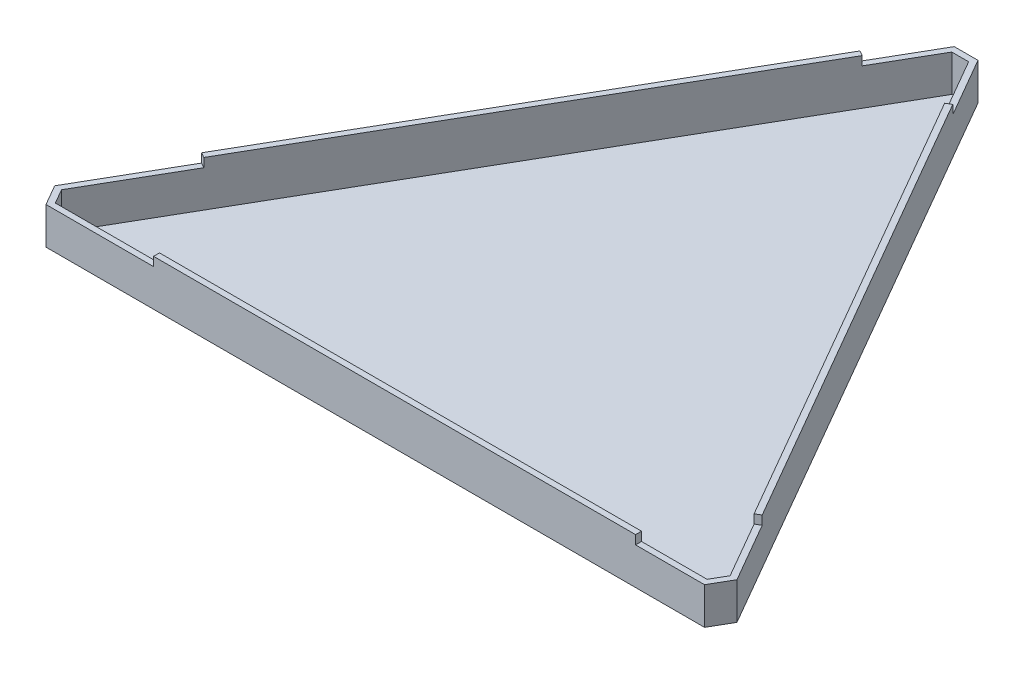
SolidWorks part; units mm, degrees
note: The reader was unsure of these and kept them because the rebuilt part matched: shared geometry of "Sketch1<3>", "Sketch1<4>".
ref_plane "Front Plane" through (0, 0, 0) normal (0, 0, 1) x (1, 0, 0)
ref_plane "Top Plane" through (0, 0, 0) normal (0, 1, 0) x (1, 0, 0)
ref_plane "Right Plane" through (0, 0, 0) normal (1, 0, 0) x (0, 0, -1)
sketch "Sketch1" plane through (0, 0, 0) normal (0, 1, 0) x (1, 0, 0)
  line L7 (-115, 0) -> (-111, -6.9282)
  line L9 (115, 0) -> (111, -6.9282)
  line L17 (-4, 192.2576) -> (111, -6.9282) construction
  line L20 (4, 192.2576) -> (-4, 192.2576)
  line L24 (4, 192.2576) -> (-111, -6.9282) construction
  line L25 (-115, 0) -> (115, 0) construction
  line L26 (-112.6906, 0) -> (-95.1379, 30.4021)
  line L27 (-113, -3.4641) -> (-107, 0) construction
  line L28 (0, 192.2576) -> (0, 185.3294) construction
  line L29 (113, -3.4641) -> (107, 0) construction
  line L30 (59.5, 96.1288) -> (57.7679, 95.1288) construction
  line L31 (-59.5, 96.1288) -> (-57.7679, 95.1288) construction
  line L33 (-112.6906, 0) -> (-109.8453, -4.9282)
  line L36 (112.6906, 0) -> (109.8453, -4.9282)
  line L37 (-2.8453, 190.2576) -> (2.8453, 190.2576)
  line L43 (87.75, -6.9282) -> (111, -6.9282)
  line L45 (87.75, -4.9282) -> (87.75, -6.9282)
  line L46 (-74.74, -4.9282) -> (87.75, -4.9282)
  line L49 (87.75, -6.9282) -> (-74.74, -6.9282)
  line L50 (-96.87, 31.4021) -> (-115, 0)
  line L51 (-15.625, 172.1225) -> (-96.87, 31.4021)
  line L52 (-15.625, 172.1225) -> (-13.8929, 171.1225)
  line L53 (-95.1379, 30.4021) -> (-13.8929, 171.1225)
  line L54 (-15.625, 172.1225) -> (-4, 192.2576)
  line L55 (-109.8453, -4.9282) -> (-74.74, -4.9282)
  line L56 (109.8453, -4.9282) -> (87.75, -4.9282)
  line L57 (-111, -6.9282) -> (-74.74, -6.9282)
  line L59 (-2.8453, 190.2576) -> (-13.8929, 171.1225)
  line L60 (115, 0) -> (103.375, 20.1351)
  line L61 (15.625, 172.1225) -> (13.8929, 171.1225)
  line L62 (103.375, 20.1351) -> (101.6429, 19.1351)
  line L63 (101.6429, 19.1351) -> (112.6906, 0)
  line L64 (2.8453, 190.2576) -> (13.8929, 171.1225)
  line L65 (4, 192.2576) -> (15.625, 172.1225)
  line L66 (15.625, 172.1225) -> (103.375, 20.1351)
  line L67 (101.6429, 19.1351) -> (13.8929, 171.1225)
  line L68 (0, -6.9282) -> (-74.74, -6.9282) construction
  line L69 (-74.74, -6.9282) -> (-74.74, -4.9282)
  line L70 (-58.634, 95.6288) -> (-96.004, 30.9021) construction
  line L71 (-96.87, 31.4021) -> (-95.1379, 30.4021)
  point P23 (-57.7679, 95.1288)
  point P28 (57.7679, 95.1288)
  point P29 (58.634, 95.6288)
  point P34 (-58.634, 95.6288)
  point P38 (14.759, 171.6225)
  point P41 (-14.759, 171.6225)
  point P44 (102.509, 19.6351)
  point P47 (-96.004, 30.9021)
  dimension "D1" = 8
  dimension "D2" = 8
  dimension "D3" = 8
  dimension "D4" = 230
  dimension "D5" = 230
  dimension "D6" = 230
  dimension "D7" = 74.74
  dimension "D8" = 2
  dimension "D9" = 2
extrude "Boss-Extrude1" add sketch "Sketch1" along normal blind 0.08
extrude "Boss-Extrude2" add sketch "Sketch1<3>" along normal blind 12.46
sketch "Sketch1<3>" plane through (0, 0, 0) normal (0, 1, 0) x (1, 0, 0) same geometry as "Sketch1"
extrude "Boss-Extrude3" add sketch "Sketch1<4>" along normal blind 15.46
sketch "Sketch1<4>" plane through (0, 0, 0) normal (0, 1, 0) x (1, 0, 0) same geometry as "Sketch1"
